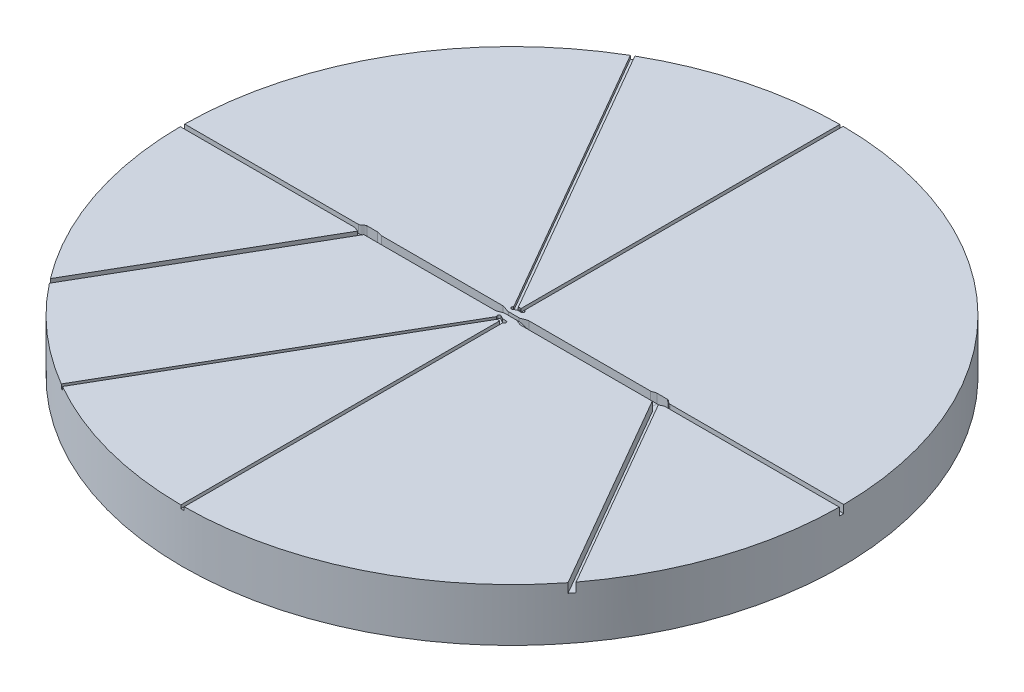
SolidWorks part; units mm, degrees
ref_plane "Front Plane" through (0, 0, 0) normal (0, 0, 1) x (1, 0, 0)
ref_plane "Top Plane" through (0, 0, 0) normal (0, 1, 0) x (1, 0, 0)
ref_plane "Right Plane" through (0, 0, 0) normal (1, 0, 0) x (0, 0, -1)
sketch "Sketch1" plane through (0, 0, 0) normal (0, 1, 0) x (1, 0, 0)
  circle A0 centre (0, 0) radius 12.5
extrude "Boss-Extrude1" add sketch "Sketch1" against normal blind 2
sketch "Sketch2" plane through (0, -2, 0) normal (0, -1, 0) x (-1, 0, 0)
  line L1 (0, 14) -> (14, 14)
  line L2 (0, 14) -> (0, -14)
  line L3 (0, -14) -> (14, -14)
  line L4 (14, 14) -> (14, -14)
extrude "Cut-Extrude1" cut sketch "Sketch2" against normal blind 3
sketch "Sketch4" plane through (0, 0, 0) normal (-1, 0, 0) x (0, 0, 1)
  line L1 (-0.0625, 0.125) -> (0.0625, 0.125)
  line L2 (-0.0625, 0.125) -> (-0.0625, -0.125)
  line L3 (-0.0625, -0.125) -> (0.0625, -0.125)
  line L4 (0.0625, 0.125) -> (0.0625, -0.125)
  line L5 (-0.0625, 0.125) -> (0.0625, -0.125) construction
  line L6 (-0.0625, -0.125) -> (0.0625, 0.125) construction
  point P0 (0, 0)
extrude "Cut-Extrude2" cut sketch "Sketch4" against normal blind 0.2
ref_plane "Plane1" through (0.5, 0, 0) normal (-1, 0, 0) x (0, 0, 1)
sketch "Sketch5" plane through (0.5, 0, 0) normal (-1, 0, 0) x (0, 0, 1)
  line L1 (-0.15, 0.3) -> (0.15, 0.3)
  line L2 (-0.15, 0.3) -> (-0.15, -0.3)
  line L3 (-0.15, -0.3) -> (0.15, -0.3)
  line L4 (0.15, 0.3) -> (0.15, -0.3)
  line L5 (-0.15, 0.3) -> (0.15, -0.3) construction
  line L6 (-0.15, -0.3) -> (0.15, 0.3) construction
  point P1 (0, 0)
extrude "Cut-Extrude3" cut sketch "Sketch5" against normal blind 5
sketch "Sketch7" plane through (0.2, 0, 0) normal (-1, 0, 0) x (0, 0, 1)
  line L1 (-0.0625, 0) -> (0.0625, 0)
  line L2 (-0.0625, 0) -> (-0.0625, -0.125)
  line L3 (-0.0625, -0.125) -> (0.0625, -0.125)
  line L4 (0.0625, 0) -> (0.0625, -0.125)
sketch "Sketch8" plane through (0.5, 0, 0) normal (-1, 0, 0) x (0, 0, 1)
  line L1 (-0.15, 0) -> (0.15, 0)
  line L2 (-0.15, 0) -> (-0.15, -0.3)
  line L3 (-0.15, -0.3) -> (0.15, -0.3)
  line L4 (0.15, 0) -> (0.15, -0.3)
loft "Cut-Loft3" cut profiles "Sketch7", "Sketch8" start constraint normal to profile start tangent length 1 end constraint normal to profile end tangent length 1 connector at (0.2, 0, 0.0625) connector at (0.5, 0, 0.15)
ref_point "Point1"
ref_axis "Axis1" through (0, 0, 0) along (1, 0, 0)
ref_plane "Plane2" through (5.5, 0, 0) normal (-1, 0, 0) x (0, 0, 1)
sketch "Sketch9" plane through (0, 0, 0) normal (0, 1, 0) x (1, 0, 0)
  line L0 (5.5, 0) -> (10.5, -8.6603)
  line L1 (5.5, 0.15) -> (5.5, -0.15) construction
ref_plane "Plane3" through (5.5, 0, 0) normal (0.5, 0, 0.866) x (0.866, 0, -0.5)
ref_plane "Plane4" through (1.425, 0, 2.4682) normal (0.5, 0, 0.866) x (0.866, 0, -0.5)
sketch "Sketch15" plane through (1.425, 0, 2.4682) normal (0.5, 0, 0.866) x (0.866, 0, -0.5)
  line L0 (0, 0) -> (4.7631, 0) construction
  line L1 (4.6631, -0.35) -> (4.8651, -0.35)
  line L2 (4.6631, -0.35) -> (4.6631, 0)
  line L3 (4.6631, 0) -> (4.8651, 0)
  line L4 (4.8651, -0.35) -> (4.8651, 0)
  line L5 (4.6631, -0.35) -> (4.8651, 0) construction
  line L6 (4.6631, 0) -> (4.8651, -0.35) construction
  point P0 (4.7641, -0.175)
extrude "Cut-Extrude4" cut sketch "Sketch15" along normal blind 10
sketch "Sketch20" plane through (5.5, 0, 0) normal (-1, 0, 0) x (0, 0, 1)
  line L1 (-0.2, 0) -> (0.15, 0)
  line L2 (-0.2, 0) -> (-0.2, -0.35)
  line L3 (-0.2, -0.35) -> (0.15, -0.35)
  line L4 (0.15, 0) -> (0.15, -0.35)
  line L5 (-0.2, 0) -> (0.15, -0.35) construction
  line L6 (-0.2, -0.35) -> (0.15, 0) construction
  point P0 (-0.025, -0.175)
extrude "Cut-Extrude7" cut sketch "Sketch20" against normal blind 0.2 and the other way blind 0.2
ref_plane "Plane5" through (5.1, 0, 0) normal (-1, 0, 0) x (0, 0, 1)
sketch "Sketch21" plane through (5.1, 0, 0) normal (-1, 0, 0) x (0, 0, 1)
  line L0 (-0.0625, 0) -> (-12.5, 0) construction
  line L1 (-0.15, 0) -> (0.15, 0)
  line L2 (-0.15, 0) -> (-0.15, -0.3)
  line L3 (-0.15, -0.3) -> (0.15, -0.3)
  line L4 (0.15, 0) -> (0.15, -0.3)
sketch "Sketch22" plane through (5.3, 0, 0) normal (1, 0, 0) x (0, 0, -1)
  line L1 (-0.15, 0) -> (0.2, 0)
  line L2 (-0.15, 0) -> (-0.15, -0.35)
  line L3 (-0.15, -0.35) -> (0.2, -0.35)
  line L4 (0.2, 0) -> (0.2, -0.35)
loft "Cut-Loft4" cut profiles "Sketch22", "Sketch21" start constraint normal to profile start tangent length 1 end constraint normal to profile end tangent length 1 connector at (5.3, 0, 0.15) connector at (5.1, 0, 0.15)
ref_plane "Plane6" through (5.9, 0, 0) normal (-1, 0, 0) x (0, 0, 1)
sketch "Sketch23" plane through (5.9, 0, 0) normal (-1, 0, 0) x (0, 0, 1)
  line L0 (-0.0625, 0) -> (-12.5, 0) construction
  line L1 (-0.085, 0) -> (0.085, 0)
  line L2 (-0.085, 0) -> (-0.085, -0.3)
  line L3 (-0.085, -0.3) -> (0.085, -0.3)
  line L4 (0.085, 0) -> (0.085, -0.3)
sketch "Sketch24" plane through (5.7, 0, 0) normal (-1, 0, 0) x (0, 0, 1)
  line L1 (0.15, 0) -> (-0.2, 0)
  line L2 (0.15, 0) -> (0.15, -0.35)
  line L3 (0.15, -0.35) -> (-0.2, -0.35)
  line L4 (-0.2, 0) -> (-0.2, -0.35)
loft "Cut-Loft5" cut profiles "Sketch24", "Sketch23" start constraint normal to profile start tangent length 1 end constraint normal to profile end tangent length 1 connector at (5.7, 0, -0.2) connector at (5.9, 0, -0.085)
extrude "Cut-Extrude8" cut sketch "Sketch23<2>" against normal blind 8
sketch "Sketch23<2>" plane through (5.9, 0, 0) normal (-1, 0, 0) x (0, 0, 1) same geometry as "Sketch23"
mirror "Mirror1" about plane through (0, 0, 0) normal (1, 0, 0) of bodies 113
ref_plane "Plane7" through (0, 0, 0.3625) normal (0, 0, -1) x (-1, 0, 0)
sketch "Sketch26" plane through (0, 0, 0.3625) normal (0, 0, -1) x (-1, 0, 0)
  line L1 (-0.0625, 0) -> (0.0625, 0)
  line L2 (-0.0625, 0) -> (-0.0625, -0.125)
  line L3 (-0.0625, -0.125) -> (0.0625, -0.125)
  line L4 (0.0625, 0) -> (0.0625, -0.125)
  line L5 (-0.0625, 0) -> (0.0625, -0.125) construction
  line L6 (-0.0625, -0.125) -> (0.0625, 0) construction
  point P0 (0, -0.0625)
extrude "Cut-Extrude9" cut sketch "Sketch26" against normal blind 13
sketch "Sketch27" plane through (0, 0, 0) normal (0, 1, 0) x (1, 0, 0)
  line L0 (0, 0) -> (-1.6943, -2.9346)
ref_plane "Plane8" through (0, 0, 0) normal (-0.5, 0, 0.866) x (0.866, 0, 0.5)
ref_point "Point2"
ref_plane "Plane9" through (-0.1726, 0, 0.2989) normal (-0.5, 0, 0.866) x (0.866, 0, 0.5)
sketch "Sketch28" plane through (-0.1726, 0, 0.2989) normal (-0.5, 0, 0.866) x (0.866, 0, 0.5)
  line L1 (-0.0625, 0) -> (0.0625, 0)
  line L2 (-0.0625, 0) -> (-0.0625, -0.125)
  line L3 (-0.0625, -0.125) -> (0.0625, -0.125)
  line L4 (0.0625, 0) -> (0.0625, -0.125)
  line L5 (-0.0625, 0) -> (0.0625, -0.125) construction
  line L6 (-0.0625, -0.125) -> (0.0625, 0) construction
  point P0 (0, -0.0625)
extrude "Cut-Extrude10" cut sketch "Sketch28" along normal blind 13
sketch "Sketch32" plane through (0, 0, 0) normal (0, 1, 0) x (1, 0, 0)
  line L0 (-0.2267, -0.2677) -> (-0.0941, -0.3443) construction
  line L1 (-1.7866, 0.6329) -> (1.4414, -1.2308) construction
  line L2 (-6.304, -10.7939) -> (-0.2267, -0.2677) construction
  line L3 (-0.1955, -0.2136) -> (-0.0773, -0.2818)
  line L4 (-0.258, -0.3218) -> (-0.1253, -0.3984)
  line L5 (-0.0941, -0.3443) -> (0.0625, -0.3443) construction
  line L6 (-0.0773, -0.2818) -> (0.0625, -0.2818)
  line L7 (-0.0941, -0.4068) -> (0.0625, -0.4068)
  line L19 (-0.2267, -0.2677) -> (-0.1185, -0.3302)
  line L20 (-0.1185, -0.3302) -> (-6.1958, -10.8564)
  line L21 (-0.0625, -12.4998) -> (-0.0625, -0.3625)
  line L22 (-0.0625, -0.3625) -> (0.0625, -0.3625)
  line L23 (0.0625, -0.3625) -> (0.0625, -12.4998)
  line L24 (9.8372, -7.7123) -> (5.4711, -0.15)
  line L25 (5.4711, -0.15) -> (0.5, -0.15)
  line L26 (0.2, -0.0625) -> (-0.2, -0.0625)
  line L27 (-0.5, -0.15) -> (-5.4711, -0.15)
  line L28 (-5.4711, -0.15) -> (-9.8372, -7.7123)
  line L29 (-6.304, -10.7939) -> (-0.2267, -0.2677)
  line L30 (-0.2267, -0.2677) -> (-0.1185, -0.3302)
  line L31 (-0.1185, -0.3302) -> (-6.1958, -10.8564)
  line L32 (-0.0625, -12.4998) -> (-0.0625, -0.3625)
  line L33 (-0.0625, -0.3625) -> (0.0625, -0.3625)
  line L34 (0.0625, -0.3625) -> (0.0625, -12.4998)
  line L35 (9.8372, -7.7123) -> (5.4711, -0.15)
  line L36 (5.4711, -0.15) -> (0.5, -0.15)
  line L37 (0.2, -0.0625) -> (-0.2, -0.0625)
  line L38 (-0.5, -0.15) -> (-5.4711, -0.15)
  line L39 (-5.4711, -0.15) -> (-9.8372, -7.7123)
  line L40 (-6.304, -10.7939) -> (-0.2267, -0.2677)
  arc A0 (-0.1955, -0.2136) -> (-0.258, -0.3218) centre (-0.2267, -0.2677) ccw
  arc A1 (-0.1253, -0.3984) -> (-0.0941, -0.4068) centre (-0.0941, -0.3443) ccw
  arc A3 (0.0625, -0.4068) -> (0.0625, -0.2818) centre (0.0625, -0.3443) ccw
  arc A7 (-6.1958, -10.8564) -> (-0.0625, -12.4998) centre (0, 0) ccw
  arc A8 (0.0625, -12.4998) -> (9.8372, -7.7123) centre (0, 0) ccw
  arc A9 (-9.8372, -7.7123) -> (-6.304, -10.7939) centre (0, 0) ccw
  arc A10 (-6.1958, -10.8564) -> (-0.0625, -12.4998) centre (0, 0) ccw
  arc A11 (0.0625, -12.4998) -> (9.8372, -7.7123) centre (0, 0) ccw
  arc A12 (-9.8372, -7.7123) -> (-6.304, -10.7939) centre (0, 0) ccw
  spline S2 degree 3 poles (432.4643, 2968.4664) (-421.6991, -2973.1923) (422.4012, 2972.995) (-431.7709, -2968.7245) knots -25.204015 -25.204015 -25.204015 -25.204015 26.204147 26.204147 26.204147 26.204147 only from (0.5, -0.15) to (0.2, -0.0625)
  spline S3 degree 3 poles (431.7643, -2968.6789) (-422.3991, 2972.9798) (421.7012, -2973.2075) (-432.4709, 2968.512) knots -25.204015 -25.204015 -25.204015 -25.204015 26.204147 26.204147 26.204147 26.204147 only from (-0.2, -0.0625) to (-0.5, -0.15)
  spline S4 degree 3 poles (0.5, -0.15) (0.3958, -0.15) (0.3042, -0.0625) (0.2, -0.0625) knots 0 0 0 0 1 1 1 1
  spline S5 degree 3 poles (-0.2, -0.0625) (-0.3042, -0.0625) (-0.3958, -0.15) (-0.5, -0.15) knots 0 0 0 0 1 1 1 1
  point P6 (-0.1604, -0.306)
  point P13 (-0.0158, -0.3443)
  dimension "D1" = 0
extrude "Cut-Extrude16" cut sketch "Sketch32" against normal blind 0.125 contours A3 L6 L3 A0 L36 L4 A1 L7 region at (-0.0775, 0, 0.3102)
mirror "Mirror2" about plane through (0, 0, 0) normal (0, 0, 1) of "Cut-Extrude16", "Cut-Extrude10", "Cut-Extrude9"
